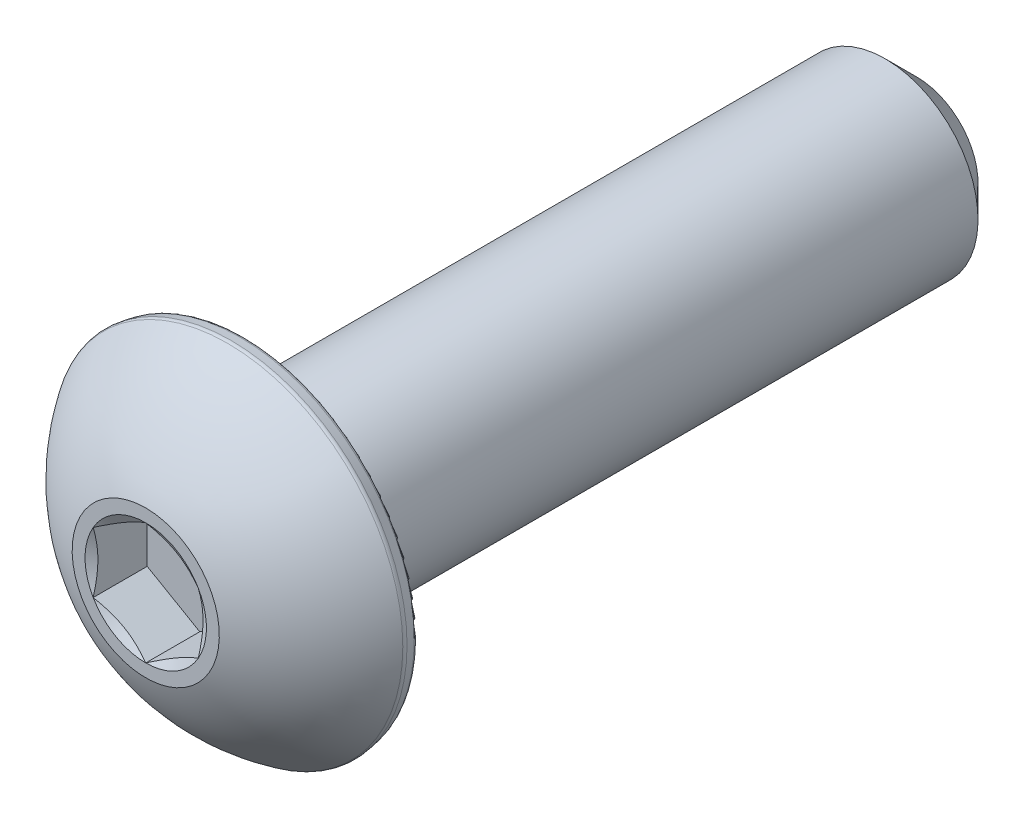
SolidWorks part; units mm, degrees
ref_plane "Front Plane" through (0, 0, 0) normal (0, 0, 1) x (1, 0, 0)
ref_plane "Top Plane" through (0, 0, 0) normal (0, 1, 0) x (1, 0, 0)
ref_plane "Right Plane" through (0, 0, 0) normal (1, 0, 0) x (0, 0, -1)
sketch "Sketch1" plane through (0, 0, 0) normal (1, 0, 0) x (0, 0, -1)
  line L0 (0, 0) -> (12.7, 0) construction
  line L1 (12.7, 1.7526) -> (12.7, -1.7526) construction
  line L2 (0, 0) -> (-1.8542, 0) construction
  line L3 (0, 3.3274) -> (0, -3.3274) construction
  line L4 (-1.8542, 0.9922) -> (-1.8542, -0.9922) construction
  line L5 (12.6504, 1.8385) -> (13.4441, 1.8385) construction
  line L6 (13.4441, 1.8385) -> (13.0473, 1.1511) construction
  line L7 (13.0473, 1.1511) -> (12.6504, 1.8385) construction
  line L8 (12.6752, 1.7956) -> (13.4193, 1.7956) construction
  line L9 (12.7, 1.7526) -> (13.3945, 1.7526) construction
  line L10 (12.9977, 1.237) -> (13.0969, 1.237) construction
  line L11 (13.0473, 1.237) -> (13.0473, 1.1511) construction
  line L12 (13.0473, 1.7526) -> (13.0473, 1.8385) construction
  point P5 (12.7, 0)
  point P10 (-1.8542, 0)
  point P13 (0, 0)
  point P18 (10.7156, -1.7526)
  point P25 (13.0473, 1.7956)
  dimension "Screw Size Decimal Equivalent" = 3.5052
  dimension "Length" = 12.7
  dimension "Head Diameter" = 6.6548
  dimension "Drive Size" = 1.9844
  dimension "Head Height" = 1.8542
  dimension "D1" = 60
  dimension "Pitch" = 0.7937
  dimension "D2" = 0.0992
  dimension "D3" = 1.9844
sketch "Sketch2" plane through (0, 0, 0) normal (1, 0, 0) x (0, 0, -1)
  line L0 (12.7, 0) -> (-1.8542, 0)
  line L1 (-1.8542, 0) -> (-1.8542, 1.3891)
  line L2 (-1.8542, 0) -> (-1.8542, 3.3274) construction
  line L3 (-1.8542, 3.3274) -> (0, 3.3274) construction
  line L4 (0, 3.2784) -> (-0.2781, 3.3274)
  line L5 (0, 3.3274) -> (0, -3.3274) construction
  line L6 (0, 3.2784) -> (0, 1.7526)
  line L7 (0, 1.7526) -> (12.1047, 1.7526)
  line L8 (12.1047, 1.7526) -> (12.7, 1.1573)
  line L9 (12.7, 1.7526) -> (12.7, -1.7526) construction
  line L10 (12.7, 1.1573) -> (12.7, 0)
  line L11 (-1.8542, 0) -> (-1.8542, -1.3891) construction
  arc A0 (-0.2781, 3.3274) -> (-1.8542, 1.3891) centre (1.8341, 0) ccw
  dimension "D1" = 45
  dimension "D2" = 0.5953
  dimension "D3" = 10
  dimension "D4" = 0.2781
  dimension "D5" = 2.7781
revolve "Revolve1" add sketch "Sketch2" angle 360 about L0
sketch "Sketch3" plane through (0, 0, 1.8542) normal (0, 0, 1) x (1, 0, 0)
  line L1 (0, 1.1457) -> (-0.9922, 0.5728)
  line L2 (-0.9922, 0.5728) -> (-0.9922, -0.5728)
  line L3 (-0.9922, -0.5728) -> (0, -1.1457)
  line L4 (0, -1.1457) -> (0.9922, -0.5728)
  line L5 (0.9922, -0.5728) -> (0.9922, 0.5728)
  line L6 (0.9922, 0.5728) -> (0, 1.1457)
  circle A0 centre (0, 0) radius 0.9922 construction
extrude "Cut-Extrude1" cut sketch "Sketch3" against normal blind 1.0198
sketch "Sketch4" plane through (0, 0, 1.8542) normal (0, 0, 1) x (1, 0, 0)
  circle A0 centre (0, 0) radius 1.1457
extrude "Cut-Extrude2" cut sketch "Sketch4" against normal blind 1.0198 draft 60
fillet "Fillet1" radius 0.0927 2 edges at (0, 3.3274, 0.2781) (0, 3.2784, 0)
sketch "Sketch8" plane through (0, 0, 0) normal (0, 0, 1) x (1, 0, 0)
  circle A0 centre (0, 0) radius 3.3274 construction
  circle A1 centre (0, 0) radius 0.9922 construction
ref_plane "Plane1" [suppressed] through (0, 0, -0.3572) normal (0, 0, 1) x (1, 0, 0)
split "Split1" [suppressed] bodies to split 106
sketch "Sketch5" [suppressed] plane through (0, 0, 0) normal (1, 0, 0) x (0, 0, -1)
  line L0 (12.6752, 1.7956) -> (13.4193, 1.7956)
  line L1 (13.4193, 1.7956) -> (13.0969, 1.237)
  line L2 (13.0969, 1.237) -> (12.9977, 1.237)
  line L3 (12.9977, 1.237) -> (12.6752, 1.7956)
sketch "Sketch6" [suppressed] plane through (0, 0, -12.7) normal (0, 0, -1) x (-1, 0, 0)
  circle A0 centre (0, 0) radius 1.7526
curve "Helix/Spiral1" [suppressed] pitch 0.7937 height 13.4937 turns 17
sweep "Cut-Sweep1" [suppressed] cut profiles "Sketch5" path "Helix/Spiral1"
combine bodies "Combine1" [suppressed] operation type add bodies to combine 109 107
sketch "Sketch7" [suppressed] plane through (0, 0, -0.3572) normal (0, 0, 1) x (1, 0, 0)
  circle A0 centre (0, 0) radius 1.7526
extrude "Boss-Extrude1" [suppressed] add sketch "Sketch7" against normal blind 1.9844 draft 45
fillet "Fillet2" [suppressed] radius 0.0927
equation "\"D2@Sketch1\"=\"Pitch@Sketch1\"/8"
equation "\"D2@Sketch2\"=\"Pitch@Sketch1\"*.75"
equation "\"D4@Sketch2\"=\"Head Height@Sketch1\"*.15"
equation "\"D5@Sketch2\"=\"Drive Size@Sketch1\"*1.4"
equation "\"D1@Cut-Extrude1\"=\"Head Height@Sketch1\"*.55"
equation "\"D1@Cut-Extrude2\"=\"D1@Cut-Extrude1\""
equation "\"D1@Fillet1\"=\"Head Height@Sketch1\"*.05"
equation "\"D4@Helix/Spiral1\"=\"Pitch@Sketch1\""
equation "\"D3@Helix/Spiral1\"=\"Length@Sketch1\"+\"Pitch@Sketch1\""
equation "\"D3@Sketch1\"=\"Pitch@Sketch1\"*2.5"
equation "\"D1@Fillet2\"=\"D1@Fillet1\""
equation "\"D1@Plane1\"=\"Pitch@Sketch1\"*.45"
equation "\"D1@Boss-Extrude1\"=\"Pitch@Sketch1\"*2.5"
